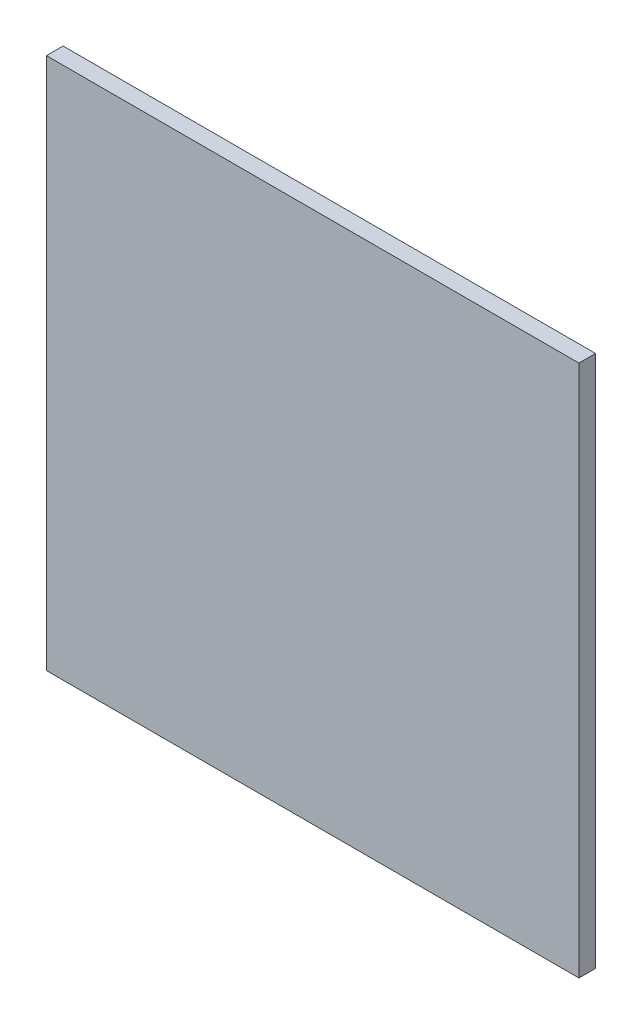
SolidWorks part; units mm, degrees
ref_plane "Front Plane" through (0, 0, 0) normal (0, 0, 1) x (1, 0, 0)
ref_plane "Top Plane" through (0, 0, 0) normal (0, 1, 0) x (1, 0, 0)
ref_plane "Right Plane" through (0, 0, 0) normal (1, 0, 0) x (0, 0, -1)
sketch "LED panel" plane through (0, 0, 0) normal (0, 0, 1) x (1, 0, 0)
  line L1 (-40, 40) -> (40, 40)
  line L2 (-40, 40) -> (-40, -40)
  line L3 (-40, -40) -> (40, -40)
  line L4 (40, 40) -> (40, -40)
  line L5 (-40, 40) -> (40, -40) construction
  line L6 (-40, -40) -> (40, 40) construction
  point P0 (0, 0)
  dimension "D1" = 80
  dimension "D2" = 80
extrude "Extrude LED panel" add sketch "LED panel" along normal blind 2.5
